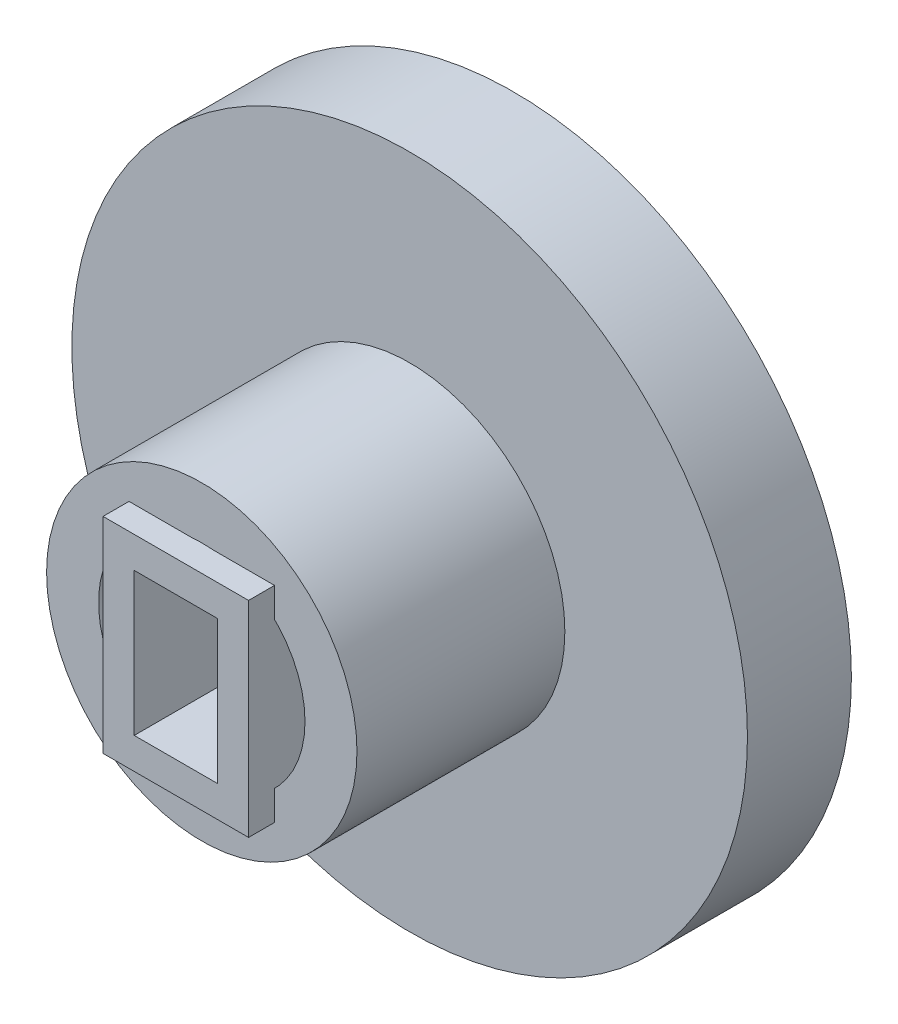
SolidWorks part; units mm, degrees
ref_plane "Front Plane" through (0, 0, 0) normal (0, 0, 1) x (1, 0, 0)
ref_plane "Top Plane" through (0, 0, 0) normal (0, 1, 0) x (1, 0, 0)
ref_plane "Right Plane" through (0, 0, 0) normal (1, 0, 0) x (0, 0, -1)
ref_plane "Plane1" through (0, 0, 5) normal (0, 0, 1) x (1, 0, 0)
ref_plane "Plane2" through (0, 0, 11) normal (0, 0, 1) x (1, 0, 0)
ref_plane "Plane3" through (0, 0, 3) normal (0, 0, 1) x (1, 0, 0)
sketch "Sketch1" plane through (0, 0, 5) normal (0, 0, 1) x (1, 0, 0)
  circle A0 centre (0, 20.9252) radius 3.9726
  circle A1 centre (0, 20.9252) radius 5
  dimension "D1" = 10
sketch "Sketch3" plane through (0, 0, 11) normal (0, 0, 1) x (1, 0, 0)
  line L0 (-3.9726, 20.9252) -> (15.3734, 20.9252) construction
  line L1 (0, 24.8978) -> (0, 8.7425) construction
  line L3 (-1.6, 23.6752) -> (1.6, 23.6752)
  line L4 (-1.6, 23.6752) -> (-1.6, 18.1752)
  line L5 (-1.6, 18.1752) -> (1.6, 18.1752)
  line L6 (1.6, 23.6752) -> (1.6, 18.1752)
  point P13 (0, 0)
  point P15 (0, 0)
  point P16 (0, 0)
  point P17 (0, 0)
  point P18 (0, 0)
  point P19 (0, 0)
  dimension "D1" = 3.2
  dimension "D2" = 5.5
  dimension "D3" = 1.6
  dimension "D4" = 2.75
extrude "Boss-Extrude1" add sketch "Sketch1" along normal blind 10 contours A0
shell "Shell1" thickness 2 removed face at (3.9726, 20.9252, 15) outward yes
extrude "Boss-Extrude2" add sketch "Sketch3" along normal blind 5 separate body
shell "Shell2" thickness 1.2 removed face at (0, 20.9252, 16) outward yes
sketch "Sketch7" plane through (0, 0, 3) normal (0, 0, -1) x (-1, 0, 0)
  line L0 (0, 14.9526) -> (0, 35.2199) construction
  line L1 (5.9726, 20.9252) -> (-26.894, 20.9252) construction
  circle A0 centre (0, 20.9252) radius 5.9726 construction
sketch "Sketch6" plane through (0, 0, 3) normal (0, 0, 1) x (1, 0, 0)
  line L1 (-4.2117, 12.2988) -> (2.2883, 12.2988)
  line L2 (-4.2117, 12.2988) -> (-4.2117, 32.2988)
  line L3 (-4.2117, 32.2988) -> (2.2883, 32.2988)
  line L4 (2.2883, 12.2988) -> (2.2883, 32.2988)
  dimension "D1" = 20
  dimension "D2" = 6.5
sketch "Sketch5" plane through (0, 0, 3) normal (0, 0, 1) x (1, 0, 0)
  line L1 (0, 14.9526) -> (0, 35.2199) construction
  line L2 (-5.9726, 20.9252) -> (26.894, 20.9252) construction
  circle A0 centre (0, 20.9252) radius 13
  point P3 (-1.3045, 18.804)
  point P4 (0, 20.9252)
extrude "Boss-Extrude3" add sketch "Sketch5" along normal blind 4 contours A0
